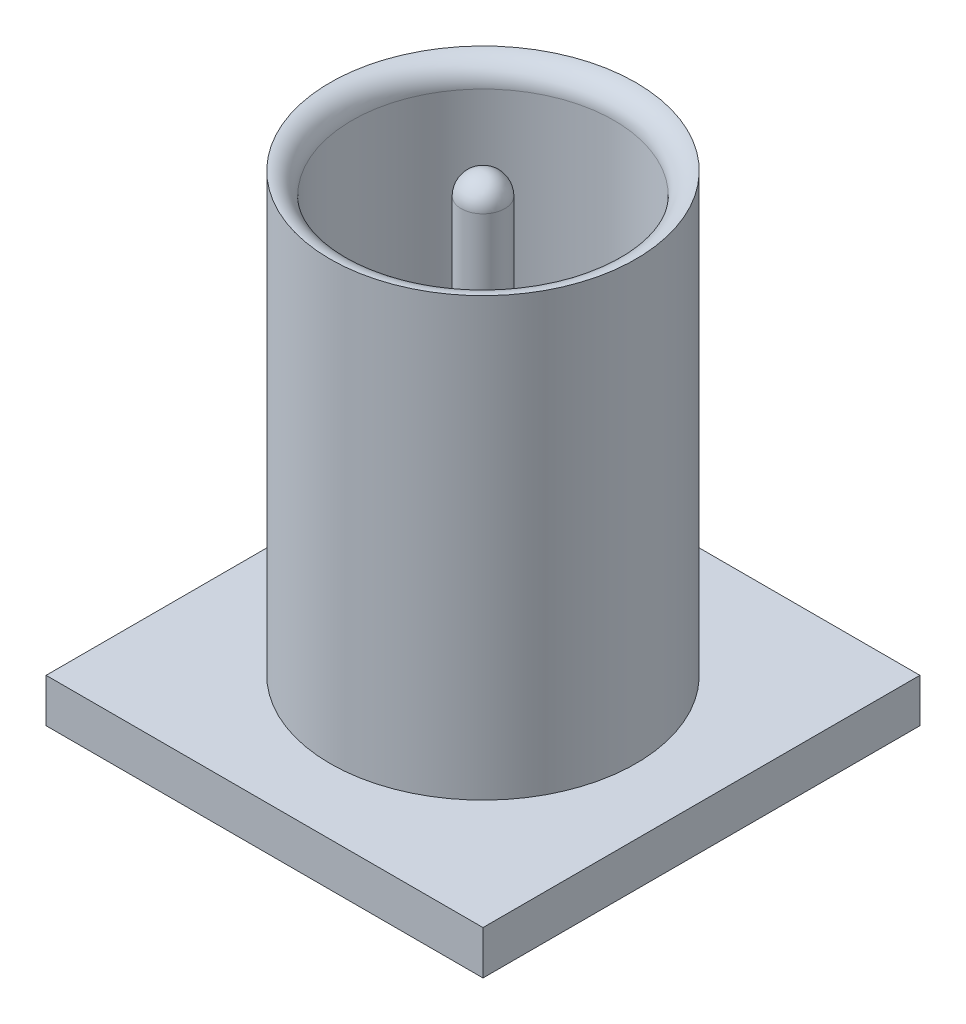
SolidWorks part; units mm, degrees
ref_plane "Front Plane" through (0, 0, 0) normal (0, 0, 1) x (1, 0, 0)
ref_plane "Top Plane" through (0, 0, 0) normal (0, 1, 0) x (1, 0, 0)
ref_plane "Right Plane" through (0, 0, 0) normal (1, 0, 0) x (0, 0, -1)
sketch "Sketch1" plane through (0, 0, 0) normal (0, 1, 0) x (1, 0, 0)
  circle A0 centre (0, 0) radius 3.5
  dimension "D1" = 7
extrude "Boss-Extrude1" add sketch "Sketch1" along normal blind 10
sketch "Sketch2" plane through (0, 10, 0) normal (0, 1, 0) x (1, 0, 0)
  circle A0 centre (0, 0) radius 3
  dimension "D1" = 6
extrude "Cut-Extrude1" cut sketch "Sketch2" against normal blind 9
sketch "Sketch3" plane through (0, 1, 0) normal (0, 1, 0) x (1, 0, 0)
  circle A0 centre (0, 0) radius 0.5
  dimension "D1" = 1
extrude "Boss-Extrude2" add sketch "Sketch3" along normal blind 9
fillet "Fillet1" radius 0.5 2 edges at (0, 10, 0.5) (0, 10, 3)
sketch "Sketch4" plane through (0, 0, 0) normal (0, -1, 0) x (-1, 0, 0)
  line L1 (-5, 5) -> (5, 5)
  line L2 (-5, 5) -> (-5, -5)
  line L3 (-5, -5) -> (5, -5)
  line L4 (5, 5) -> (5, -5)
  line L5 (-5, 5) -> (5, -5) construction
  line L6 (-5, -5) -> (5, 5) construction
  point P0 (0, 0)
  dimension "D1" = 10
extrude "Boss-Extrude3" add sketch "Sketch4" along normal blind 1
